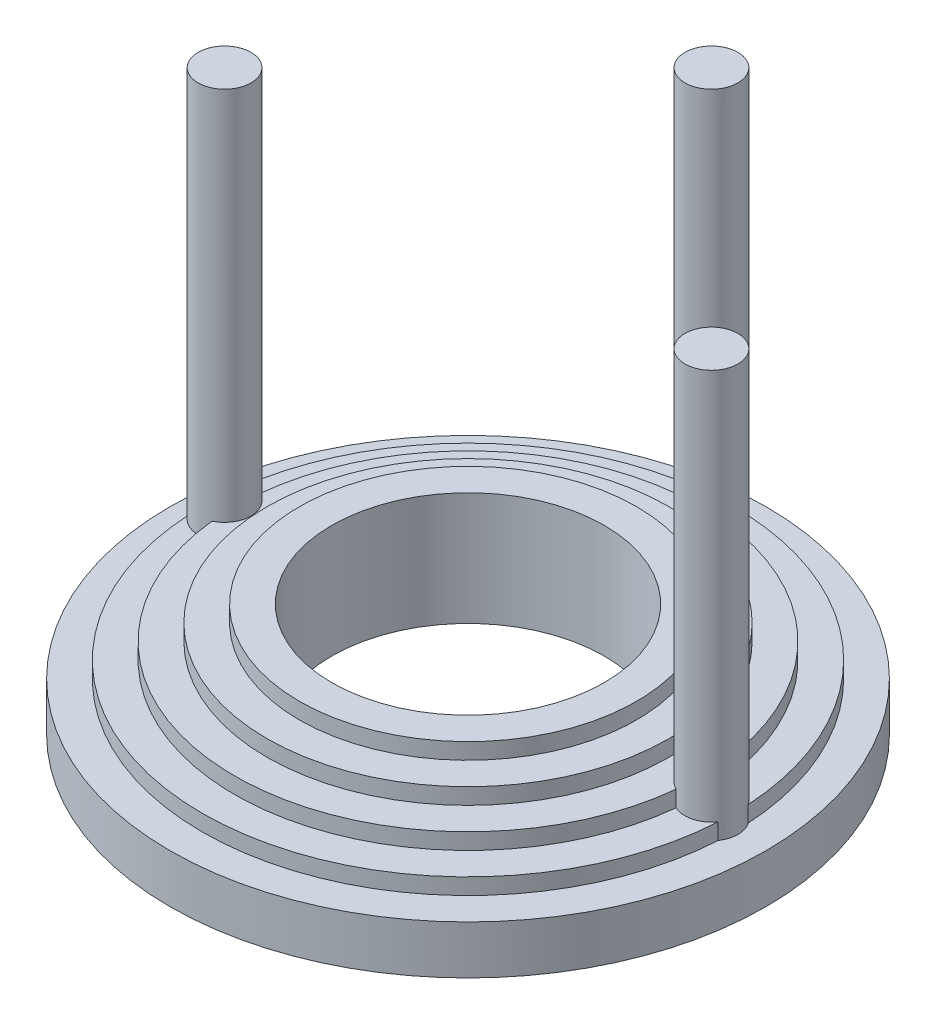
SolidWorks part; units mm, degrees
material "Copper"
ref_plane "Front Plane" through (0, 0, 0) normal (0, 0, 1) x (1, 0, 0)
ref_plane "Top Plane" through (0, 0, 0) normal (0, 1, 0) x (1, 0, 0)
ref_plane "Right Plane" through (0, 0, 0) normal (1, 0, 0) x (0, 0, -1)
sketch "Sketch1" plane through (0, 0, 0) normal (0, 0, 1) x (1, 0, 0)
  line L0 (0, 0) -> (0, 44.8786) construction
  line L1 (-48.224, 35.0971) -> (-40.462, 35.0971)
  line L2 (-48.224, 35.0971) -> (-48.224, 31.2161)
  line L3 (-48.224, 31.2161) -> (-55.986, 31.2161)
  line L4 (-55.986, 31.2161) -> (-55.986, 27.3351)
  line L5 (-55.986, 27.3351) -> (-63.748, 27.3351)
  line L6 (-63.748, 27.3351) -> (-63.748, 23.4541)
  line L7 (-63.748, 23.4541) -> (-71.51, 23.4541)
  line L8 (-71.51, 23.4541) -> (-71.51, 11.8111)
  line L9 (-71.51, 11.8111) -> (-32.7, 11.8111)
  line L10 (-32.7, 11.8111) -> (-32.7, 35.0971)
  line L11 (-40.462, 35.0971) -> (-40.462, 38.9781)
  line L12 (-40.462, 38.9781) -> (-32.7, 38.9781)
  line L13 (-32.7, 38.9781) -> (-32.7, 35.0971)
  dimension "D1" = 3.881
  dimension "D2" = 3.881
  dimension "D3" = 3.881
  dimension "D4" = 11.643
  dimension "D5" = 3.881
  dimension "D6" = 7.762
  dimension "D7" = 7.762
  dimension "D8" = 7.762
  dimension "D9" = 7.762
  dimension "D10" = 7.762
  dimension "D11" = 65.4
revolve "Revolve1" add sketch "Sketch1" angle 360 about L0
sketch "Sketch2" plane through (0, 38.9781, 0) normal (0, 1, 0) x (1, 0, 0)
  point P0 (0, -31.414)
  point P1 (0, -34.286)
sketch "Sketch3" plane through (0, 35.0971, 0) normal (0, 1, 0) x (1, 0, 0)
  point P0 (0, -38.913)
  point P1 (0, -42.1041)
sketch "Sketch5" plane through (0, 23.4541, 0) normal (0, 1, 0) x (1, 0, 0)
  point P0 (0, -62.6865)
  point P1 (0, -65.8775)
sketch "Sketch6" plane through (0, 31.2161, 0) normal (0, 1, 0) x (1, 0, 0)
  point P0 (0, -46.6373)
  point P1 (0, -49.893)
sketch "Sketch7" plane through (0, 27.3351, 0) normal (0, 1, 0) x (1, 0, 0)
  point P0 (0, -54.4509)
  point P1 (0, -57.7066)
other "CPoint2" parameters "Diameter"=3.175, "StubLength"=0
ref_axis "Axis2" through (0, 48.9781, 31.414) along (0, -1, 0)
other "CPoint3" parameters "Diameter"=3.175, "StubLength"=0
ref_axis "Axis3" through (0, 48.9781, 34.286) along (0, -1, 0)
other "CPoint4" parameters "Diameter"=3.175, "StubLength"=0
ref_axis "Axis4" through (0, 45.0971, 38.913) along (0, -1, 0)
other "CPoint5" parameters "Diameter"=3.175, "StubLength"=0
ref_axis "Axis5" through (0, 45.0971, 42.1041) along (0, -1, 0)
other "CPoint6" parameters "Diameter"=3.175, "StubLength"=0
ref_axis "Axis6" through (0, 41.2161, 46.6373) along (0, -1, 0)
other "CPoint7" parameters "Diameter"=3.175, "StubLength"=0
ref_axis "Axis7" through (0, 41.2161, 49.893) along (0, -1, 0)
other "CPoint8" parameters "Diameter"=3.175, "StubLength"=0
ref_axis "Axis8" through (0, 37.3351, 54.4509) along (0, -1, 0)
other "CPoint9" parameters "Diameter"=3.175, "StubLength"=0
ref_axis "Axis9" through (0, 37.3351, 57.7066) along (0, -1, 0)
other "CPoint10" parameters "Diameter"=3.175, "StubLength"=0
ref_axis "Axis10" through (0, 33.4541, 62.6865) along (0, -1, 0)
other "CPoint11" parameters "Diameter"=3.175, "StubLength"=0
ref_axis "Axis11" through (0, 33.4541, 65.8775) along (0, -1, 0)
sketch "Sketch8" plane through (0, 23.4541, 0) normal (0, 1, 0) x (1, 0, 0)
  line L0 (0, -3.0305) -> (0, 76.4411) construction
  line L1 (0, 0) -> (88.099, 0) construction
  circle A0 centre (-58.42, 0) radius 6.35
  circle A1 centre (58.42, 0) radius 6.35
  circle A2 centre (0, 58.42) radius 6.35
  dimension "D1" = 12.7
  dimension "D2" = 12.7
  dimension "D3" = 58.42
  dimension "D4" = 58.42
extrude "Extrude1" add sketch "Sketch8" along normal blind 97.79
